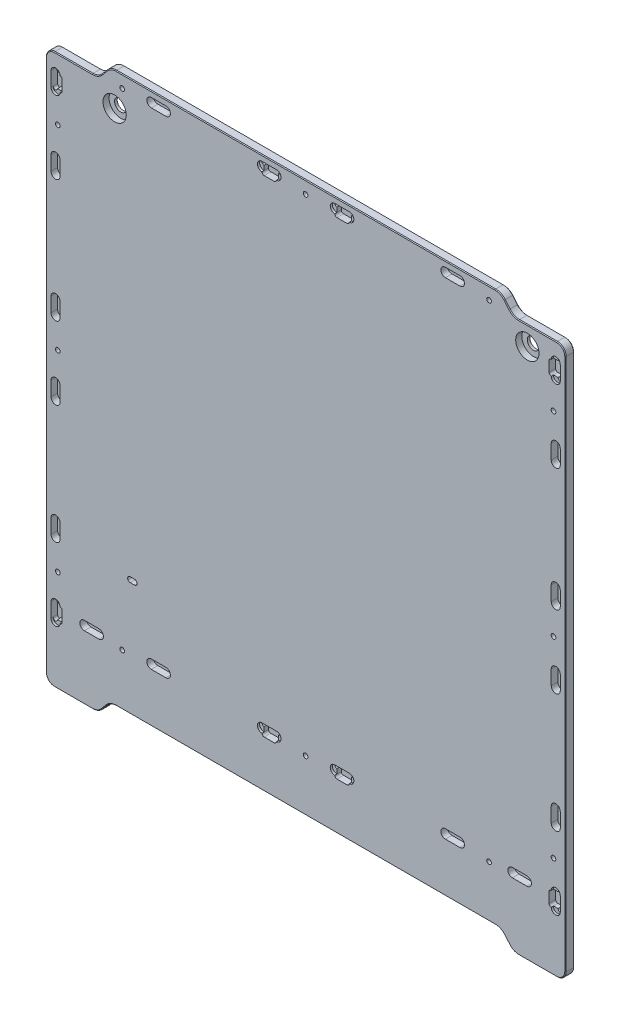
SolidWorks part; units mm, degrees
ref_plane "Alzado" through (0, 0, 0) normal (0, 0, 1) x (1, 0, 0)
ref_plane "Planta" through (0, 0, 0) normal (0, 1, 0) x (1, 0, 0)
ref_plane "Vista lateral" through (0, 0, 0) normal (1, 0, 0) x (0, 0, -1)
ref_plane "Plano1" through (0, 0, 3) normal (0, 0, 1) x (1, 0, 0)
sketch "Croquis1" plane through (0, 0, 3) normal (0, 0, 1) x (1, 0, 0)
  line L0 (-178.5, 194) -> (-178.5, -194)
  line L1 (-178.5, -194) -> (178.5, -194)
  line L2 (178.5, -194) -> (178.5, 194)
  line L3 (178.5, 194) -> (-178.5, 194)
  dimension "D1" = 357
  dimension "D2" = 388
extrude "Saliente-Extruir1" add sketch "Croquis1" against normal blind 6
sketch "Croquis2" plane through (0, 0, 3) normal (0, 0, 1) x (1, 0, 0)
  line L0 (-20, 182.4) -> (-20, 183.9)
  line L1 (-20, 190.1) -> (-30, 190.1)
  line L2 (-30, 183.9) -> (-30, 182.4)
  line L3 (-30, 182.4) -> (-20, 182.4)
  line L4 (-178.5, 194) -> (-178.5, -194) construction
  line L5 (178.5, 194) -> (-178.5, 194) construction
  arc A0 (-20, 183.9) -> (-20, 190.1) centre (-20, 187) ccw
  arc A1 (-30, 190.1) -> (-30, 183.9) centre (-30, 187) ccw
  dimension "D1" = 3.1
  dimension "D2" = 148.5
  dimension "D3" = 158.5
  dimension "D4" = 7
extrude "Cortar-Extruir1" cut sketch "Croquis2" against normal blind 1.5
sketch "Croquis3" plane through (0, 0, 1.5) normal (0, 0, 1) x (1, 0, 0)
  line L0 (-20, 190.1) -> (-30, 190.1)
  line L1 (-30, 187.1) -> (-30, 182.4)
  line L2 (-30, 182.4) -> (-20, 182.4)
  line L3 (-20, 182.4) -> (-20, 187.1)
  line L4 (-20, 182.4) -> (-20, 183.9) construction
  arc A0 (-20, 187.1) -> (-20, 190.1) centre (-20, 188.6) ccw
  arc A1 (-30, 190.1) -> (-30, 187.1) centre (-30, 188.6) ccw
  dimension "D1" = 1.5
  dimension "D2" = 10
extrude "Cortar-Extruir2" cut sketch "Croquis3" against normal blind 3
sketch "Croquis4" plane through (0, 0, 3) normal (0, 0, 1) x (1, 0, 0)
  line L0 (-167.2, 171.7) -> (-168.7, 171.7)
  line L1 (-174.9, 171.7) -> (-174.9, 161.7)
  line L2 (-168.7, 161.7) -> (-167.2, 161.7)
  line L3 (-167.2, 161.7) -> (-167.2, 171.7)
  line L4 (-30, 183.9) -> (-30, 182.4) construction
  line L5 (-30, 182.4) -> (-20, 182.4) construction
  arc A0 (-168.7, 171.7) -> (-174.9, 171.7) centre (-171.8, 171.7) ccw
  arc A1 (-174.9, 161.7) -> (-168.7, 161.7) centre (-171.8, 161.7) ccw
  dimension "D1" = 3.1
  dimension "D2" = 137.2
  dimension "D3" = 141.8
  dimension "D4" = 10.7
extrude "Cortar-Extruir3" cut sketch "Croquis4" against normal blind 1.5
sketch "Croquis5" plane through (0, 0, 1.5) normal (0, 0, 1) x (1, 0, 0)
  line L0 (-171.9, 161.7) -> (-167.2, 161.7)
  line L1 (-167.2, 161.7) -> (-167.2, 171.7)
  line L2 (-167.2, 171.7) -> (-171.9, 171.7)
  line L3 (-174.9, 171.7) -> (-174.9, 161.7)
  line L4 (-167.2, 161.7) -> (-167.2, 171.7) construction
  arc A0 (-171.9, 171.7) -> (-174.9, 171.7) centre (-173.4, 171.7) ccw
  arc A1 (-174.9, 161.7) -> (-171.9, 161.7) centre (-173.4, 161.7) ccw
  dimension "D1" = 1.5
  dimension "D2" = 6.2
extrude "Cortar-Extruir4" cut sketch "Croquis5" against normal blind 3
sketch "Croquis6" plane through (0, 0, 3) normal (0, 0, 1) x (1, 0, 0)
  line L0 (-167.2, -144.2) -> (-168.7, -144.2)
  line L1 (-174.9, -144.2) -> (-174.9, -154.2)
  line L2 (-168.7, -154.2) -> (-167.2, -154.2)
  line L3 (-167.2, -154.2) -> (-167.2, -144.2)
  line L4 (-174.9, 171.7) -> (-174.9, 161.7) construction
  line L5 (-168.7, 161.7) -> (-167.2, 161.7) construction
  arc A0 (-168.7, -144.2) -> (-174.9, -144.2) centre (-171.8, -144.2) ccw
  arc A1 (-174.9, -154.2) -> (-168.7, -154.2) centre (-171.8, -154.2) ccw
  dimension "D1" = 3.1
  dimension "D2" = 305.9
  dimension "D3" = 7.7
  dimension "D4" = 315.9
extrude "Cortar-Extruir5" cut sketch "Croquis6" against normal blind 1.5
sketch "Croquis7" plane through (0, 0, 1.5) normal (0, 0, 1) x (1, 0, 0)
  line L0 (-171.9, -154.2) -> (-167.2, -154.2)
  line L1 (-167.2, -154.2) -> (-167.2, -144.2)
  line L2 (-167.2, -144.2) -> (-171.9, -144.2)
  line L3 (-174.9, -144.2) -> (-174.9, -154.2)
  line L4 (-167.2, -154.2) -> (-167.2, -144.2) construction
  arc A0 (-171.9, -144.2) -> (-174.9, -144.2) centre (-173.4, -144.2) ccw
  arc A1 (-174.9, -154.2) -> (-171.9, -154.2) centre (-173.4, -154.2) ccw
  dimension "D1" = 1.5
  dimension "D2" = 6.2
extrude "Cortar-Extruir6" cut sketch "Croquis7" against normal blind 3
sketch "Croquis8" plane through (0, 0, 3) normal (0, 0, 1) x (1, 0, 0)
  line L0 (-20, -151.6) -> (-20, -150.1)
  line L1 (-20, -143.9) -> (-30, -143.9)
  line L2 (-30, -150.1) -> (-30, -151.6)
  line L3 (-30, -151.6) -> (-20, -151.6)
  line L4 (-167.2, -154.2) -> (-167.2, -144.2) construction
  line L5 (-168.7, -154.2) -> (-167.2, -154.2) construction
  arc A0 (-20, -150.1) -> (-20, -143.9) centre (-20, -147) ccw
  arc A1 (-30, -143.9) -> (-30, -150.1) centre (-30, -147) ccw
  dimension "D1" = 3.1
  dimension "D2" = 137.2
  dimension "D3" = 147.2
  dimension "D4" = 2.6
  dimension "D5" = 7.2
extrude "Cortar-Extruir7" cut sketch "Croquis8" against normal blind 1.5
sketch "Croquis9" plane through (0, 0, 1.5) normal (0, 0, 1) x (1, 0, 0)
  line L0 (-30, -146.9) -> (-30, -151.6)
  line L1 (-30, -151.6) -> (-20, -151.6)
  line L2 (-20, -151.6) -> (-20, -146.9)
  line L3 (-20, -143.9) -> (-30, -143.9)
  line L4 (-20, -151.6) -> (-20, -150.1) construction
  arc A0 (-30, -143.9) -> (-30, -146.9) centre (-30, -145.4) ccw
  arc A1 (-20, -146.9) -> (-20, -143.9) centre (-20, -145.4) ccw
  dimension "D1" = 1.5
  dimension "D2" = 10
extrude "Cortar-Extruir8" cut sketch "Croquis9" against normal blind 3
sketch "Croquis10" plane through (0, 0, -3) normal (0, 0, -1) x (-1, 0, 0)
  line L0 (134.1086, 194) -> (134.1086, 183.9996)
  line L1 (134.1086, 183.9996) -> (178.5, 183.9996)
  line L2 (178.5, 183.9996) -> (178.5, 194)
  line L3 (178.5, 194) -> (134.1086, 194)
  line L4 (-178.5, -194) -> (-178.5, 194) construction
  line L5 (-178.5, 194) -> (178.5, 194) construction
  dimension "D1" = 312.6086
  dimension "D2" = 357
  dimension "D3" = 10.0004
extrude "Cortar-Extruir9" cut sketch "Croquis10" against normal through all
sketch "Croquis11" plane through (0, 0, -3) normal (0, 0, -1) x (-1, 0, 0)
  line L0 (-134.1086, -194) -> (134.1086, -194)
  line L1 (134.1086, -194) -> (134.1086, -183.9996)
  line L2 (134.1086, -183.9996) -> (-134.1086, -183.9996)
  line L3 (-134.1086, -183.9996) -> (-134.1086, -194)
  line L4 (178.5, 183.9996) -> (178.5, -194) construction
  line L5 (134.1086, 183.9996) -> (178.5, 183.9996) construction
  dimension "D1" = 44.3914
  dimension "D2" = 312.6086
  dimension "D3" = 367.9992
  dimension "D4" = 377.9996
extrude "Cortar-Extruir10" cut sketch "Croquis11" against normal through all
sketch "Croquis12" plane through (0, 0, -3) normal (0, 0, -1) x (-1, 0, 0)
  line L0 (120.5, -102.25) -> (117.5, -102.25)
  line L1 (117.5, -105.75) -> (120.5, -105.75)
  line L2 (134.1086, -194) -> (134.1086, -183.9996) construction
  line L3 (178.5, -194) -> (134.1086, -194) construction
  arc A0 (117.5, -102.25) -> (117.5, -105.75) centre (117.5, -104) ccw
  arc A1 (120.5, -105.75) -> (120.5, -102.25) centre (120.5, -104) ccw
  dimension "D1" = 1.75
  dimension "D2" = 13.6086
  dimension "D3" = 16.6086
  dimension "D4" = 90
extrude "Cortar-Extruir11" cut sketch "Croquis12" against normal through all
sketch "Croquis13" plane through (0, 0, 3) normal (0, 0, 1) x (1, 0, 0)
  line L0 (-106, 183.9) -> (-96, 183.9)
  line L1 (-96, 190.1) -> (-106, 190.1)
  line L2 (-178.5, 183.9996) -> (-178.5, -194) construction
  line L3 (-178.5, -194) -> (-134.1086, -194) construction
  arc A0 (-96, 183.9) -> (-96, 190.1) centre (-96, 187) ccw
  arc A1 (-106, 190.1) -> (-106, 183.9) centre (-106, 187) ccw
  dimension "D1" = 3.1
  dimension "D2" = 72.5
  dimension "D3" = 82.5
  dimension "D4" = 381
extrude "Cortar-Extruir12" cut sketch "Croquis13" against normal blind 4.5
sketch "Croquis14" plane through (0, 0, 3) normal (0, 0, 1) x (1, 0, 0)
  line L0 (-168.7, 111.7) -> (-168.7, 121.7)
  line L1 (-174.9, 121.7) -> (-174.9, 111.7)
  line L2 (-178.5, 183.9996) -> (-178.5, -194) construction
  line L3 (-178.5, -194) -> (-134.1086, -194) construction
  arc A0 (-174.9, 111.7) -> (-168.7, 111.7) centre (-171.8, 111.7) ccw
  arc A1 (-168.7, 121.7) -> (-174.9, 121.7) centre (-171.8, 121.7) ccw
  dimension "D1" = 3.1
  dimension "D2" = 6.7
  dimension "D3" = 305.7
  dimension "D4" = 315.7
extrude "Cortar-Extruir13" cut sketch "Croquis14" against normal blind 4.5
sketch "Croquis15" plane through (0, 0, 3) normal (0, 0, 1) x (1, 0, 0)
  line L0 (-168.7, 27.5) -> (-168.7, 37.5)
  line L1 (-174.9, 37.5) -> (-174.9, 27.5)
  line L2 (-178.5, 183.9996) -> (-178.5, -194) construction
  line L3 (-178.5, -194) -> (-134.1086, -194) construction
  arc A0 (-174.9, 27.5) -> (-168.7, 27.5) centre (-171.8, 27.5) ccw
  arc A1 (-168.7, 37.5) -> (-174.9, 37.5) centre (-171.8, 37.5) ccw
  dimension "D1" = 3.1
  dimension "D2" = 6.7
  dimension "D3" = 221.5
  dimension "D4" = 231.5
extrude "Cortar-Extruir14" cut sketch "Croquis15" against normal blind 4.5
sketch "Croquis16" plane through (0, 0, 3) normal (0, 0, 1) x (1, 0, 0)
  line L0 (-168.7, -22.5) -> (-168.7, -12.5)
  line L1 (-174.9, -12.5) -> (-174.9, -22.5)
  line L2 (-178.5, 183.9996) -> (-178.5, -194) construction
  line L3 (-178.5, -194) -> (-134.1086, -194) construction
  arc A0 (-174.9, -22.5) -> (-168.7, -22.5) centre (-171.8, -22.5) ccw
  arc A1 (-168.7, -12.5) -> (-174.9, -12.5) centre (-171.8, -12.5) ccw
  dimension "D1" = 3.1
  dimension "D2" = 6.7
  dimension "D3" = 171.5
  dimension "D4" = 181.5
extrude "Cortar-Extruir15" cut sketch "Croquis16" against normal blind 4.5
sketch "Croquis17" plane through (0, 0, 3) normal (0, 0, 1) x (1, 0, 0)
  line L0 (-168.7, -104.2) -> (-168.7, -94.2)
  line L1 (-174.9, -94.2) -> (-174.9, -104.2)
  line L2 (178.5, -194) -> (178.5, 194) construction
  line L3 (134.1086, -194) -> (178.5, -194) construction
  arc A0 (-174.9, -104.2) -> (-168.7, -104.2) centre (-171.8, -104.2) ccw
  arc A1 (-168.7, -94.2) -> (-174.9, -94.2) centre (-171.8, -94.2) ccw
  dimension "D1" = 3.1
  dimension "D2" = 350.3
  dimension "D3" = 89.8
  dimension "D4" = 99.8
extrude "Cortar-Extruir16" cut sketch "Croquis17" against normal blind 4.5
sketch "Croquis18" plane through (0, 0, 3) normal (0, 0, 1) x (1, 0, 0)
  line L0 (-106, -150.1) -> (-96, -150.1)
  line L1 (-96, -143.9) -> (-106, -143.9)
  line L2 (178.5, -194) -> (178.5, 194) construction
  line L3 (134.1086, -194) -> (178.5, -194) construction
  arc A0 (-96, -150.1) -> (-96, -143.9) centre (-96, -147) ccw
  arc A1 (-106, -143.9) -> (-106, -150.1) centre (-106, -147) ccw
  dimension "D1" = 3.1
  dimension "D2" = 274.5
  dimension "D3" = 284.5
  dimension "D4" = 47
extrude "Cortar-Extruir17" cut sketch "Croquis18" against normal blind 4.5
sketch "Croquis19" plane through (0, 0, 3) normal (0, 0, 1) x (1, 0, 0)
  line L0 (-152, -150.1) -> (-142, -150.1)
  line L1 (-142, -143.9) -> (-152, -143.9)
  line L2 (178.5, -194) -> (178.5, 194) construction
  line L3 (134.1086, -194) -> (178.5, -194) construction
  arc A0 (-142, -150.1) -> (-142, -143.9) centre (-142, -147) ccw
  arc A1 (-152, -143.9) -> (-152, -150.1) centre (-152, -147) ccw
  dimension "D1" = 3.1
  dimension "D2" = 320.5
  dimension "D3" = 330.5
  dimension "D4" = 47
extrude "Cortar-Extruir18" cut sketch "Croquis19" against normal blind 4.5
mirror "Simetría1" about plane through (0, 0, 0) normal (1, 0, 0) of "Cortar-Extruir15", "Cortar-Extruir1", "Cortar-Extruir2", "Cortar-Extruir3", "Cortar-Extruir4", "Cortar-Extruir5", "Cortar-Extruir6", "Cortar-Extruir7", "Cortar-Extruir8", "Cortar-Extruir9", "Cortar-Extruir12", "Cortar-Extruir13", "Cortar-Extruir14", "Cortar-Extruir16", "Cortar-Extruir17", "Cortar-Extruir18"
draft "Ángulo de salida1" type of draft neutral plane draft angle 40 faces to draft 2 face at (134.1086, 188.9998, 0) face at (-134.1086, 188.9998, 0) neutral plane through (178.5, 194, -3) neutral plane normal (0, 1, 0) parameters "D1"=40
draft "Ángulo de salida2" type of draft neutral plane draft angle 40 faces to draft 2 face at (-134.1086, -188.9998, 0) face at (134.1086, -188.9998, 0) neutral plane through (-134.1086, -183.9996, 3) neutral plane normal (0, -1, 0) parameters "D1"=40
hole_wizard "Diámetro de taladro Ø3.2 (3.2)1" positions "Croquis22" profile "Croquis21" hole size "Ø3.2" standard "Ansi Metric"
sketch "Croquis22" plane through (0, 0, 3) normal (0, 0, 1) x (1, 0, 0)
  point P0 (170.25, -124.3)
  point P1 (170.25, 7.6)
  point P2 (170.25, 141.7)
  point P3 (126, 185.45)
  point P4 (126, -148.55)
sketch "Croquis21" plane through (170.25, -124.3, 3) normal (1, 0, 0) x (0, -1, 0)
  line L0 (0, 0) -> (0, 6)
  line L1 (0, 6) -> (1.6, 6)
  line L2 (1.6, 6) -> (1.6, 0)
  line L5 (1.6, 0) -> (0, 0)
  line L11 (0, -6.35) -> (0, 107.95) construction
  dimension "Diámetro de taladro hasta el siguiente" = 3.2
  dimension "Profundidad de taladro hasta el siguiente" = 6
hole_wizard "Diámetro de taladro Ø3.2 (3.2)2" positions "Croquis24" profile "Croquis23" hole size "Ø3.2" standard "Ansi Metric"
sketch "Croquis24" plane through (0, 0, -3) normal (0, 0, -1) x (-1, 0, 0)
  point P0 (0, 185.45)
  point P1 (0, -148.55)
  point P2 (170.25, -124.3)
  point P3 (170.25, 7.6)
  point P4 (170.25, 141.7)
  point P5 (126, 185.45)
  point P6 (126, -148.55)
sketch "Croquis23" plane through (0, 185.45, -3) normal (1, 0, 0) x (0, 1, 0)
  line L0 (0, 0) -> (0, 6)
  line L1 (0, 6) -> (1.6, 6)
  line L2 (1.6, 6) -> (1.6, 0)
  line L5 (1.6, 0) -> (0, 0)
  line L11 (0, -6.35) -> (0, 107.95) construction
  dimension "Diámetro de taladro hasta el siguiente" = 3.2
  dimension "Profundidad de taladro hasta el siguiente" = 6
hole_wizard "Refrentado para perno con cabeza hexagonal de M81" positions "Croquis26" profile "Croquis25" counterbore size "M8" standard "Ansi Metric"
sketch "Croquis26" plane through (0, 0, 3) normal (0, 0, 1) x (1, 0, 0)
  point P0 (-131.2, 171)
  point P1 (152.3, 171)
sketch "Croquis25" plane through (-131.2, 171, 3) normal (1, 0, 0) x (0, -1, 0)
  line L0 (0, 0) -> (0, 6)
  line L1 (0, 6) -> (4.25, 6)
  line L3 (4.25, 6) -> (4.25, 4.2)
  line L4 (4.25, 4.2) -> (8, 4.2)
  line L5 (8, 4.2) -> (8, 0)
  line L7 (8, 0) -> (0, 0)
  line L11 (0, -6.35) -> (0, 107.95) construction
  dimension "Diámetro de taladro hasta el siguiente" = 8.5
  dimension "Profundidad de taladro hasta el siguiente" = 6
  dimension "Diámetro de refrentado" = 16
  dimension "Profundidad de refrentado" = 4.2
fillet "Redondeo1" radius 6 4 edges at (178.5, 183.9996, 0) (-178.5, 183.9996, 0) (-178.5, -194, 0) (178.5, -194, 0) tangent propagation no
fillet "Redondeo2" radius 8.5 8 edges at (134.1086, 194, 0) (-142.5, 183.9996, 0) (142.5, 183.9996, 0) (142.5, -194, 0) (-134.1086, 194, 0) (134.1086, -183.9996, 0) (-134.1086, -183.9996, 0) (-142.5, -194, 0) tangent propagation no
chamfer "Chaflán1" distance 0.5 angle 45 48 edges at (133.7373, 193.2036, -3) (0, 194, -3) (138.3043, 188.9998, -3) (-133.7373, 193.2036, -3) (142.8714, 184.796, -3) (-138.3043, 188.9998, -3) (159.4818, 183.9996, -3) (-142.8714, 184.796, -3) (176.7426, 182.2422, -3) (-159.4818, 183.9996, -3) (178.5, -5.0002, -3) (-176.7426, 182.2422, -3) (176.7426, -192.2426, -3) (-178.5, -5.0002, -3) (159.4818, -194, -3) (-176.7426, -192.2426, -3) (142.8714, -193.2036, -3) (-159.4818, -194, -3) (138.3043, -188.9998, -3) (-142.8714, -193.2036, -3) (133.7373, -184.796, -3) (-138.3043, -188.9998, -3) (0, -183.9996, -3) (-133.7373, -184.796, -3) (-159.4818, 183.9996, 3) (-142.8714, 184.796, 3) (-176.7426, 182.2422, 3) (-138.3043, 188.9998, 3) (-178.5, -5.0002, 3) (-133.7373, 193.2036, 3) (-176.7426, -192.2426, 3) (0, 194, 3) (-159.4818, -194, 3) (133.7373, 193.2036, 3) (-142.8714, -193.2036, 3) (138.3043, 188.9998, 3) (-138.3043, -188.9998, 3) (142.8714, 184.796, 3) (-133.7373, -184.796, 3) (159.4818, 183.9996, 3) (0, -183.9996, 3) (176.7426, 182.2422, 3) (133.7373, -184.796, 3) (178.5, -5.0002, 3) (138.3043, -188.9998, 3) (176.7426, -192.2426, 3) (142.8714, -193.2036, 3) (159.4818, -194, 3)
fillet "Redondeo3" radius 1.5 16 edges at (167.2, -144.2, 0.75) (20, 182.4, 0.75) (-30, -151.6, 0.75) (167.2, -154.2, 0.75) (167.2, 171.7, 0.75) (30, -151.6, 0.75) (-167.2, -144.2, 0.75) (-30, 182.4, 0.75) (-20, -151.6, 0.75) (-20, 182.4, 0.75) (30, 182.4, 0.75) (-167.2, 161.7, 0.75) (167.2, 161.7, 0.75) (-167.2, 171.7, 0.75) (-167.2, -154.2, 0.75) (20, -151.6, 0.75) tangent propagation no
